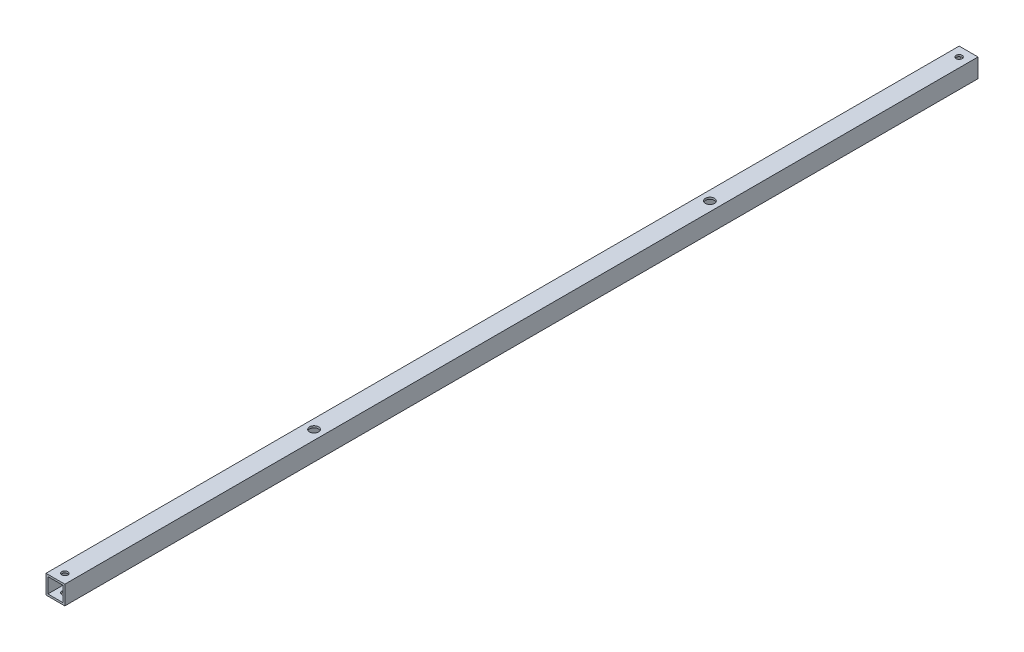
SolidWorks part; units mm, degrees
ref_plane "正面" through (0, 0, 0) normal (0, 0, 1) x (1, 0, 0)
ref_plane "平面" through (0, 0, 0) normal (0, 1, 0) x (1, 0, 0)
ref_plane "右側面" through (0, 0, 0) normal (1, 0, 0) x (0, 0, -1)
sketch "ｽｹｯﾁ1" plane through (0, 0, 0) normal (0, 0, 1) x (1, 0, 0)
  line L1 (0, 0) -> (10, 0)
  line L2 (0, 0) -> (0, 10)
  line L3 (0, 10) -> (10, 10)
  line L4 (10, 0) -> (10, 10)
  line L5 (1, 1) -> (9, 1)
  line L6 (1, 1) -> (1, 9)
  line L7 (1, 9) -> (9, 9)
  line L8 (9, 1) -> (9, 9)
extrude "ﾎﾞｽ - 押し出し1" add sketch "ｽｹｯﾁ1" along normal blind 242.229
sketch "ｽｹｯﾁ2" plane through (0, 10, 0) normal (0, 1, 0) x (1, 0, 0)
  line L1 (10, -242.229) -> (0, -242.229) construction
  circle A1 centre (5, -137.229) radius 2.4
  circle A2 centre (5, -5) radius 1.6
  dimension "D2" = 105
  dimension "D3" = 132.229
extrude "ｶｯﾄ - 押し出し1" cut sketch "ｽｹｯﾁ2" against normal through all contours A2 | A1 region at (5, 10, 137.229) region at (5, 10, 5)
mirror "ﾐﾗｰ1" about plane through (0, 0, 242.229) normal (0, 0, -1) of bodies 102
